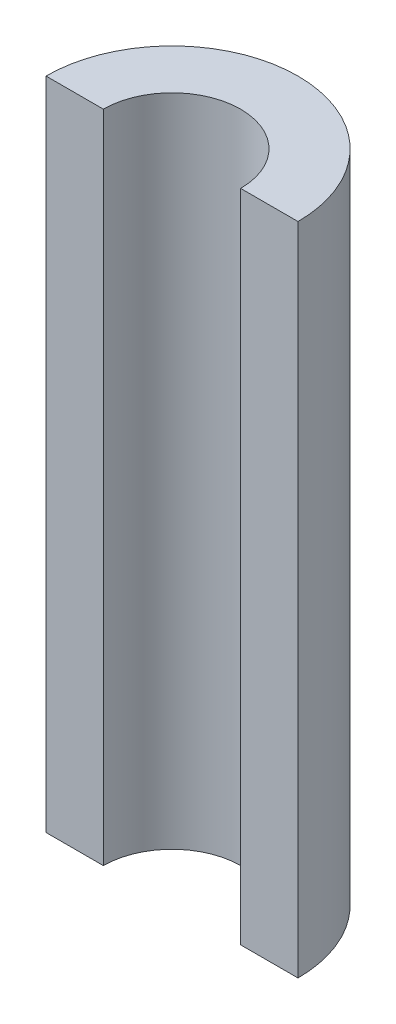
SolidWorks part; units mm, degrees
material "Expanded Polystyrene (EPS)"
ref_plane "Front Plane" through (0, 0, 0) normal (1, 0, 0) x (0, 1, 0)
ref_plane "Top Plane" through (0, 0, 0) normal (0, 0, 1) x (0, 1, 0)
ref_plane "Right Plane" through (0, 0, 0) normal (0, 1, 0) x (-1, 0, 0)
sketch "Sketch1" plane through (0, 0, 0) normal (0, 1, 0) x (-1, 0, 0)
  line L0 (-41.275, 0) -> (41.275, 0)
  arc A0 (-41.275, 0) -> (41.275, 0) centre (0, 0) ccw
  point P5 (0, 0)
  dimension "D1" = 82.55
extrude "Boss-Extrude1" add sketch "Sketch1" along normal mid plane 214.63 contours A0 L0
sketch "Sketch3" plane through (0, 107.315, 0) normal (0, 1, 0) x (-1, 0, 0)
  circle A0 centre (0, 0) radius 22.479
  dimension "D1" = 44.958
extrude "Cut-Extrude1" cut sketch "Sketch3" against normal through all both and the other way through all
